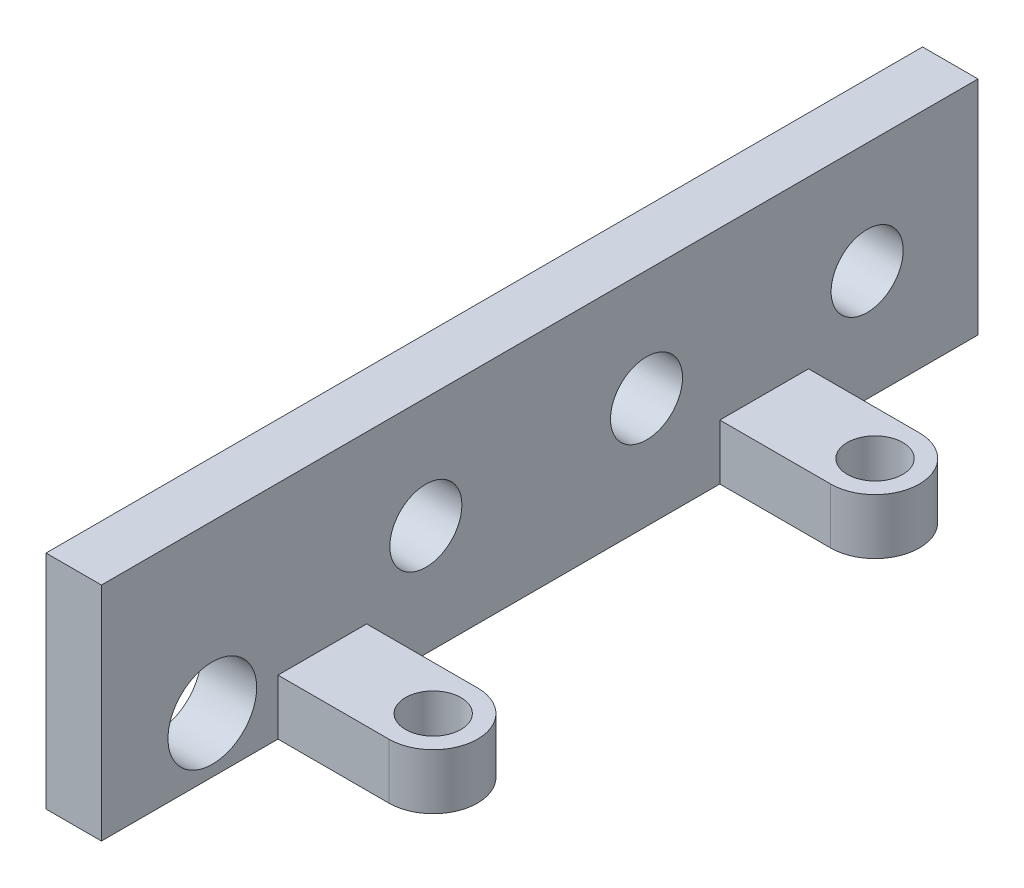
SolidWorks part; units mm, degrees
ref_plane "Front Plane" through (0, 0, 0) normal (0, 0, 1) x (1, 0, 0)
ref_plane "Top Plane" through (0, 0, 0) normal (0, 1, 0) x (1, 0, 0)
ref_plane "Right Plane" through (0, 0, 0) normal (1, 0, 0) x (0, 0, -1)
sketch "Sketch1" plane through (0, 0, 0) normal (1, 0, 0) x (0, 0, -1)
  line L1 (0, 0) -> (-79.0616, 0)
  line L2 (0, 0) -> (0, 20)
  line L3 (0, 20) -> (-79.0616, 20)
  line L4 (-79.0616, 0) -> (-79.0616, 20)
  circle A0 centre (-29.9, 10) radius 3.25
  circle A1 centre (-49.8, 10) radius 3.25
  circle A2 centre (-69.0616, 5) radius 4
  circle A3 centre (-10, 10) radius 3.25
  point P11 (0, 0)
  point P14 (0, 0)
  point P15 (-69.7, 5.4587)
  dimension "D1" = 10
  dimension "D3" = 6.5
  dimension "D4" = 10
  dimension "D10" = 8
  dimension "D2" = 20
  dimension "D5" = 19.9
  dimension "D6" = 19.9
  dimension "D7" = 10
  dimension "D8" = 5
  dimension "D9" = 19.9
extrude "Boss-Extrude1" add sketch "Sketch1" along normal blind 5
sketch "Sketch2" plane through (5, 0, 0) normal (1, 0, 0) x (0, 0, -1)
  line L0 (-79.0616, 0) -> (-39.2116, 0)
  line L2 (-79.0616, 0) -> (0, 0) construction
  line L3 (0, 20) -> (-79.0616, 20) construction
  line L4 (-15.2866, 5) -> (-23.2866, 5)
  line L5 (-15.2866, 0) -> (-15.2866, 5)
  line L6 (-63.1366, 0) -> (-55.1366, 0)
  line L7 (-63.1366, 0) -> (-63.1366, 5)
  line L8 (-63.1366, 5) -> (-55.1366, 5)
  line L9 (-55.1366, 5) -> (-55.1366, 0)
  line L10 (-39.2116, 0) -> (-39.2116, 20) construction
  line L13 (-15.2866, 0) -> (-23.2866, 0)
  line L14 (-23.2866, 5) -> (-23.2866, 0)
  point P2 (-59.1366, 0)
  point P5 (-59.1366, 0)
  dimension "D1" = 39.85
  dimension "D5" = 8
  dimension "D6" = 5
extrude "Boss-Extrude2" add sketch "Sketch2" along normal blind 10 contours L9 L6 L7 L8 | L4 L14 L13 L5
sketch "Sketch3" plane through (0, 5, 0) normal (0, 1, 0) x (1, 0, 0)
  line L0 (15, -55.1366) -> (15, -63.1366)
  arc A0 (15, -55.1366) -> (15, -63.1366) centre (15, -59.1366) cw
  circle A1 centre (15, -59.1366) radius 2.5
  dimension "D1" = 5
extrude "Boss-Extrude3" add sketch "Sketch3" against normal blind 5 contours A0 L0
extrude "Cut-Extrude2" cut sketch "Sketch3<6>" against normal through all contours A1
sketch "Sketch3<6>" plane through (0, 5, 0) normal (0, 1, 0) x (1, 0, 0) same geometry as "Sketch3"
ref_plane "Plane1" through (0, 0, 39.2116) normal (0, 0, 1) x (1, 0, 0)
mirror "Mirror1" about plane through (0, 0, 39.2116) normal (0, 0, 1) of "Boss-Extrude3", "Cut-Extrude2"
